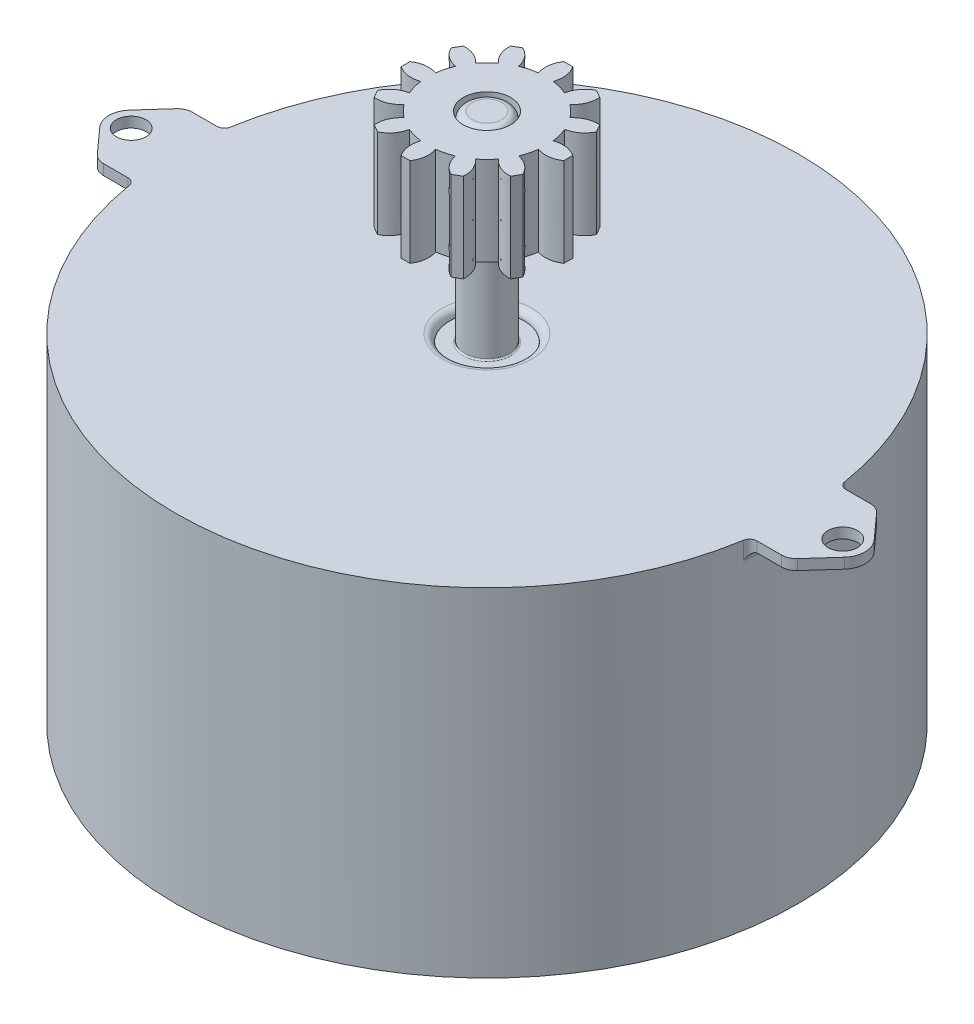
SolidWorks part; units mm, degrees
ref_plane "Front Plane" through (0, 0, 0) normal (0, 0, 1) x (1, 0, 0)
ref_plane "Top Plane" through (0, 0, 0) normal (0, 1, 0) x (1, 0, 0)
ref_plane "Right Plane" through (0, 0, 0) normal (1, 0, 0) x (0, 0, -1)
sketch "Sketch1" plane through (0, 0, 0) normal (0, 1, 0) x (1, 0, 0)
  circle A0 centre (0, 0) radius 21
extrude "Boss-Extrude1" add sketch "Sketch1" along normal blind 22.8
sketch "Sketch2" plane through (0, 22.8, 0) normal (0, 1, 0) x (1, 0, 0)
  circle A0 centre (0, 0) radius 1.5
extrude "Boss-Extrude2" add sketch "Sketch2" along normal blind 13
sketch "Sketch3" plane through (0, 22.8, 0) normal (0, 1, 0) x (1, 0, 0)
  circle A0 centre (0, 0) radius 2.5
  circle A1 centre (0, 0) radius 1.5
extrude "Cut-Extrude1" cut sketch "Sketch3" against normal blind 0.5
fillet "Fillet1" radius 0.1 1 edges at (0, 22.3, 1.5)
fillet "Fillet2" radius 0.5 1 edges at (0, 22.8, 2.5)
fillet "Fillet3" radius 0.5 1 edges at (0, 35.8, 1.5)
sketch "Sketch4" plane through (0, 22.8, 0) normal (0, 1, 0) x (1, 0, 0)
  line L0 (-25.5, 0) -> (25.5, 0) construction
  line L1 (0, 8.0058) -> (0, -5.3801) construction
  line L2 (-25.1147, 1.0037) -> (-23.6152, 2.6691)
  line L3 (-22.872, 3) -> (-20.7846, 3)
  line L4 (-24, 0) -> (-25.1147, 1.0037) construction
  line L5 (-22.872, -3) -> (-20.7846, -3)
  line L6 (-25.1147, -1.0037) -> (-23.6152, -2.6691)
  line L7 (24, 0) -> (25.1147, 1.0037) construction
  line L8 (25.1147, -1.0037) -> (23.6152, -2.6691)
  line L9 (22.872, -3) -> (20.7846, -3)
  line L10 (22.872, 3) -> (20.7846, 3)
  line L11 (25.1147, 1.0037) -> (23.6152, 2.6691)
  circle A0 centre (-24, 0) radius 1
  arc A1 (-25.1147, 1.0037) -> (-25.1147, -1.0037) centre (-24, 0) ccw
  arc A2 (-23.6152, 2.6691) -> (-22.872, 3) centre (-22.872, 2) cw
  arc A3 (-20.7846, 3) -> (-20.7846, -3) centre (0, 0) ccw
  arc A4 (-23.6152, -2.6691) -> (-22.872, -3) centre (-22.872, -2) ccw
  circle A5 centre (0, 0) radius 21 construction
  arc A6 (23.6152, -2.6691) -> (22.872, -3) centre (22.872, -2) cw
  arc A7 (20.7846, 3) -> (20.7846, -3) centre (0, 0) cw
  arc A8 (23.6152, 2.6691) -> (22.872, 3) centre (22.872, 2) ccw
  arc A9 (25.1147, 1.0037) -> (25.1147, -1.0037) centre (24, 0) cw
  circle A10 centre (24, 0) radius 1
  dimension "D2" = 24
  dimension "D4" = 1
  dimension "D1" = 51
  dimension "D3" = 42
  dimension "D5" = 3
extrude "Boss-Extrude3" add sketch "Sketch4" against normal blind 0.7
fillet "Fillet4" radius 0.5 6 edges at (20.7846, 22.45, -3) (20.7846, 22.45, 3) (21, 22.1, 0) (-20.7846, 22.45, -3) (-20.7846, 22.45, 3) (-21, 22.1, 0)
sketch "Sketch7" plane through (0, 35.8, 0) normal (0, 1, 0) x (1, 0, 0)
  line L0 (0, 0) -> (0, 5.4973) construction
  line L2 (-0.3, 5.4891) -> (0.3, 5.4891)
  line L3 (2.4847, 4.9037) -> (3.0043, 4.6037)
  line L4 (4.6037, 3.0043) -> (4.9037, 2.4847)
  line L5 (5.4891, 0.3) -> (5.4891, -0.3)
  line L6 (4.9037, -2.4847) -> (4.6037, -3.0043)
  line L7 (3.0043, -4.6037) -> (2.4847, -4.9037)
  line L8 (0.3, -5.4891) -> (-0.3, -5.4891)
  line L9 (-2.4847, -4.9037) -> (-3.0043, -4.6037)
  line L10 (-4.6037, -3.0043) -> (-4.9037, -2.4847)
  line L11 (-5.4891, -0.3) -> (-5.4891, 0.3)
  line L12 (-4.9037, 2.4847) -> (-4.6037, 3.0043)
  line L13 (-3.0043, 4.6037) -> (-2.4847, 4.9037)
  circle A1 centre (0, 0) radius 1.6
  circle A3 centre (0, 0) radius 1.6
  circle A4 centre (0, 0) radius 1.6
  circle A5 centre (0, 0) radius 1.6
  circle A6 centre (0, 0) radius 1.6
  circle A7 centre (0, 0) radius 1.6
  circle A8 centre (0, 0) radius 1.6
  circle A9 centre (0, 0) radius 1.6
  circle A10 centre (0, 0) radius 1.6
  circle A11 centre (0, 0) radius 1.6
  circle A12 centre (0, 0) radius 1.6
  circle A13 centre (0, 0) radius 1.6
  arc A14 (-2.416, 3.1847) -> (-3.1847, 2.416) centre (0, 0) ccw
  arc A15 (-0.5, 3.966) -> (-1.55, 3.6847) centre (0, 0) ccw
  arc A16 (1.55, 3.6847) -> (0.5, 3.966) centre (0, 0) ccw
  arc A17 (3.1847, 2.416) -> (2.416, 3.1847) centre (0, 0) ccw
  arc A18 (-1.55, -3.6847) -> (-0.5, -3.966) centre (0, 0) ccw
  arc A19 (0.5, -3.966) -> (1.55, -3.6847) centre (0, 0) ccw
  arc A20 (2.416, -3.1847) -> (3.1847, -2.416) centre (0, 0) ccw
  arc A21 (3.6847, -1.55) -> (3.966, -0.5) centre (0, 0) ccw
  arc A22 (3.966, 0.5) -> (3.6847, 1.55) centre (0, 0) ccw
  arc A23 (-3.1847, -2.416) -> (-2.416, -3.1847) centre (0, 0) ccw
  arc A24 (-3.966, -0.5) -> (-3.6847, -1.55) centre (0, 0) ccw
  arc A25 (-3.6847, 1.55) -> (-3.966, 0.5) centre (0, 0) ccw
  spline S0 degree 2 poles (-0.3, 5.4891) (-0.7602, 4.7921) (-0.5, 3.966) knots 0 0 0 1 1 1
  spline S1 degree 2 poles (0.3, 5.4891) (0.7602, 4.7921) (0.5, 3.966) knots 0 0 0 1 1 1
  spline S2 degree 2 poles (2.4847, 4.9037) (1.7377, 4.5302) (1.55, 3.6847) knots 0 0 0 1 1 1
  spline S3 degree 2 poles (3.0043, 4.6037) (3.0544, 3.77) (2.416, 3.1847) knots 0 0 0 1 1 1
  spline S4 degree 2 poles (4.6037, 3.0043) (3.77, 3.0544) (3.1847, 2.416) knots 0 0 0 1 1 1
  spline S5 degree 2 poles (4.9037, 2.4847) (4.5302, 1.7377) (3.6847, 1.55) knots 0 0 0 1 1 1
  spline S6 degree 2 poles (5.4891, 0.3) (4.7921, 0.7602) (3.966, 0.5) knots 0 0 0 1 1 1
  spline S7 degree 2 poles (5.4891, -0.3) (4.7921, -0.7602) (3.966, -0.5) knots 0 0 0 1 1 1
  spline S8 degree 2 poles (4.9037, -2.4847) (4.5302, -1.7377) (3.6847, -1.55) knots 0 0 0 1 1 1
  spline S9 degree 2 poles (4.6037, -3.0043) (3.77, -3.0544) (3.1847, -2.416) knots 0 0 0 1 1 1
  spline S10 degree 2 poles (3.0043, -4.6037) (3.0544, -3.77) (2.416, -3.1847) knots 0 0 0 1 1 1
  spline S11 degree 2 poles (2.4847, -4.9037) (1.7377, -4.5302) (1.55, -3.6847) knots 0 0 0 1 1 1
  spline S12 degree 2 poles (0.3, -5.4891) (0.7602, -4.7921) (0.5, -3.966) knots 0 0 0 1 1 1
  spline S13 degree 2 poles (-0.3, -5.4891) (-0.7602, -4.7921) (-0.5, -3.966) knots 0 0 0 1 1 1
  spline S14 degree 2 poles (-2.4847, -4.9037) (-1.7377, -4.5302) (-1.55, -3.6847) knots 0 0 0 1 1 1
  spline S15 degree 2 poles (-3.0043, -4.6037) (-3.0544, -3.77) (-2.416, -3.1847) knots 0 0 0 1 1 1
  spline S16 degree 2 poles (-4.6037, -3.0043) (-3.77, -3.0544) (-3.1847, -2.416) knots 0 0 0 1 1 1
  spline S17 degree 2 poles (-4.9037, -2.4847) (-4.5302, -1.7377) (-3.6847, -1.55) knots 0 0 0 1 1 1
  spline S18 degree 2 poles (-5.4891, -0.3) (-4.7921, -0.7602) (-3.966, -0.5) knots 0 0 0 1 1 1
  spline S19 degree 2 poles (-5.4891, 0.3) (-4.7921, 0.7602) (-3.966, 0.5) knots 0 0 0 1 1 1
  spline S20 degree 2 poles (-4.9037, 2.4847) (-4.5302, 1.7377) (-3.6847, 1.55) knots 0 0 0 1 1 1
  spline S21 degree 2 poles (-4.6037, 3.0043) (-3.77, 3.0544) (-3.1847, 2.416) knots 0 0 0 1 1 1
  spline S22 degree 2 poles (-3.0043, 4.6037) (-3.0544, 3.77) (-2.416, 3.1847) knots 0 0 0 1 1 1
  spline S23 degree 2 poles (-2.4847, 4.9037) (-1.7377, 4.5302) (-1.55, 3.6847) knots 0 0 0 1 1 1
  point P90 (0, 0)
  dimension "D1" = 1
  dimension "D2" = 0.6
  dimension "D3" = 12
extrude "Boss-Extrude5" add sketch "Sketch7" against normal blind 6 separate body contours A1 L2 S0 A15 S23 L13 S22 A14 S21 L12 S20 A25 S19 L11 S18 A24 S17 L10 S16 A23 S15 L9 S14 A18 S13 L8 S12 A19 S11 L7 S10 A20 S9 L6 S8 A21 S7 L5 S6 A22 S5 L4 S4 A17 S3 L3 S2 A16 S1 region at (0, 35.8, -5.3338)
